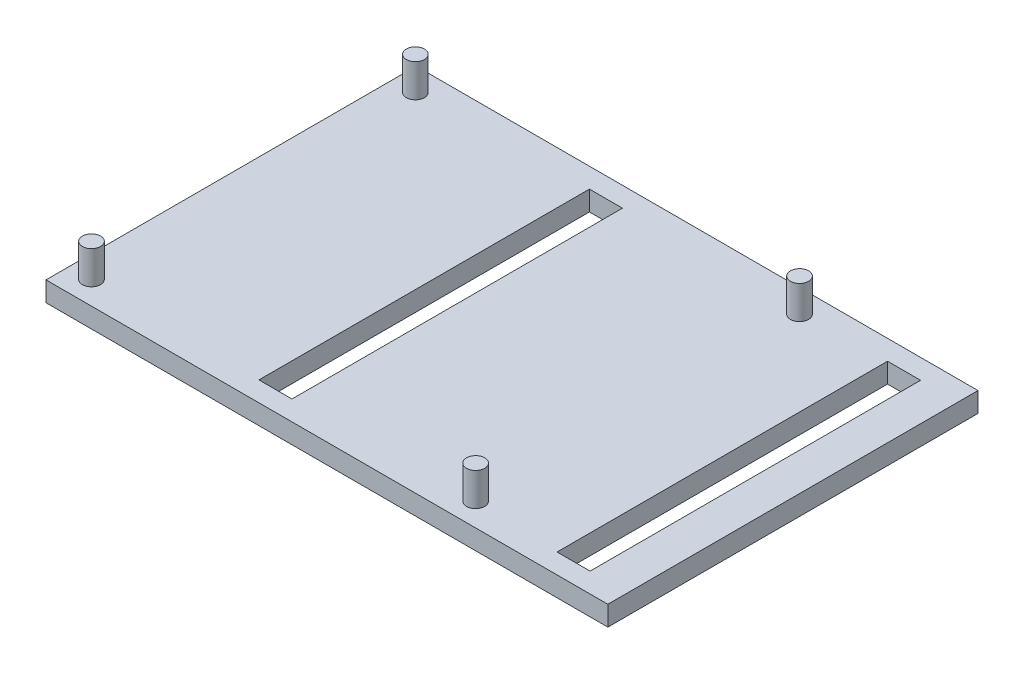
SolidWorks part; units mm, degrees
ref_plane "Plan de face" through (0, 0, 0) normal (0, 0, 1) x (1, 0, 0)
ref_plane "Plan de dessus" through (0, 0, 0) normal (0, 1, 0) x (1, 0, 0)
ref_plane "Plan de droite" through (0, 0, 0) normal (1, 0, 0) x (0, 0, -1)
sketch "Esquisse1" plane through (0, 0, 0) normal (0, 1, 0) x (1, 0, 0)
  line L0 (-42.5, 0) -> (16.7085, 0) construction
  line L1 (42.5, 28) -> (-42.5, 28)
  line L2 (42.5, 28) -> (42.5, -28)
  line L3 (42.5, -28) -> (-42.5, -28)
  line L4 (-42.5, 28) -> (-42.5, -28)
  line L5 (42.5, 28) -> (-42.5, -28) construction
  line L6 (42.5, -28) -> (-42.5, 28) construction
  line L7 (11.7629, 23.5878) -> (11.7629, -18.0665) construction
  line L8 (-8.2876, 25) -> (-13.2876, 25)
  line L9 (-8.2876, 25) -> (-8.2876, -25)
  line L10 (-8.2876, -25) -> (-13.2876, -25)
  line L11 (-13.2876, 25) -> (-13.2876, -25)
  line L12 (-8.2876, 25) -> (-13.2876, -25) construction
  line L13 (-8.2876, -25) -> (-13.2876, 25) construction
  line L14 (31.8133, -25) -> (36.8133, -25)
  line L15 (31.8133, 25) -> (31.8133, -25)
  line L16 (31.8133, 25) -> (36.8133, 25)
  line L17 (36.8133, 25) -> (36.8133, -25)
  point P0 (0, 0)
  point P6 (-10.7876, 0)
  dimension "D1" = 85
  dimension "D2" = 56
  dimension "D3" = 5
  dimension "D4" = 50
extrude "BASE" add sketch "Esquisse1" along normal blind 3
sketch "Esquisse2" plane through (0, 3, 0) normal (0, 1, 0) x (1, 0, 0)
  line L0 (-39, 28.0707) -> (-39, -34.4186) construction
  line L1 (-42.5, 0) -> (-27.7014, 0) construction
  line L2 (-42.5, 28) -> (-42.5, -28) construction
  line L3 (19, 24.5) -> (19, -25.5337) construction
  circle A0 centre (-39.1183, 24.5) radius 1.375
  circle A1 centre (-39.1183, -24.5) radius 1.375
  circle A2 centre (19, 24.5) radius 1.375
  circle A3 centre (19, -24.5) radius 1.375
  point P0 (-39.1183, 24.5)
  point P1 (-39, -24.5)
  point P2 (19, -24.5)
  point P3 (19, 24.5)
  dimension "D4" = 2.75
  dimension "D8" = 2.75
  dimension "D1" = 24.5
  dimension "D2" = 24.5
  dimension "D3" = 3.5
  dimension "D5" = 24.5
  dimension "D6" = 24.5
  dimension "D7" = 58
extrude "BOSS - ENTRETOISE" add sketch "Esquisse2" along normal blind 5
sketch "Esquisse3" plane through (0, 0, 0) normal (0, -1, 0) x (1, 0, 0)
  circle A0 centre (19, 24.5) radius 1.375 construction
  circle A1 centre (19, 24.5) radius 1.375
  circle A2 centre (19, -24.5) radius 1.375 construction
  circle A3 centre (-39.1183, -24.5) radius 1.375 construction
  circle A4 centre (-39.1183, 24.5) radius 1.375 construction
  circle A5 centre (19, -24.5) radius 1.375
  circle A6 centre (-39.1183, -24.5) radius 1.375
  circle A7 centre (-39.1183, 24.5) radius 1.375
extrude "Enlèv. mat.-Extru.1" cut sketch "Esquisse3" against normal up to surface (3 mm away) up to face at (19, 3, -25.875)
ref_axis "AXE ENTRETOISE 1" through (19, 3, -24.5) along (0, -1, 0)
ref_axis "AXE ENTRETOISE 2" through (-39.1183, 3, -24.5) along (0, -1, 0)
ref_plane "PLAN ENTRETOISE" through (0, 0, -24.5) normal (0, 0, 1) x (1, 0, 0)
sketch "Esquisse4" plane through (0, 0, -24.5) normal (0, 0, 1) x (1, 0, 0)
  line L0 (19, 3) -> (19, 0) construction
  line L1 (42.5, 0) -> (-42.5, 0) construction
  line L2 (20.375, 3) -> (20.375, 0) construction
  line L3 (19, 2) -> (20.375, 2)
  line L4 (21.76, 0) -> (19, 0)
  line L6 (42.5, 3) -> (-42.5, 3) construction
  line L7 (19, 3) -> (19, 0) construction
  line L9 (20.375, 2) -> (21.76, 0)
  line L14 (19, 2) -> (19, 0)
  point P0 (19, 2)
  dimension "D1" = 2
  dimension "D2" = 1.375
  dimension "D3" = 2.76
revolve "VIDE VIS 1" cut sketch "Esquisse4" angle 360 about L7
sketch "Esquisse5" plane through (0, 0, -24.5) normal (0, 0, 1) x (1, 0, 0)
  line L0 (42.5, 0) -> (-42.5, 0) construction
  line L1 (-39.1183, 2) -> (-37.7433, 2)
  line L2 (-37.7433, 2) -> (-36.3583, 0)
  line L3 (-39.1183, 3) -> (-39.1183, 0) construction
  line L4 (-36.3583, 0) -> (-39.1183, 0)
  line L5 (-39.1183, 0) -> (-39.1183, 2)
  line L6 (-37.7433, 3) -> (-37.7433, -0.329) construction
  point P0 (-39.1183, 2)
  point P5 (-36.3583, 0)
  point P7 (-39.1183, 0)
  dimension "D1" = 2
  dimension "D2" = 2.76
revolve "VIDE VIS 2" cut sketch "Esquisse5" angle 360 about axis through (-39.1183, 3, -24.5) along (0, -1, 0)
mirror "SYM VIS" about plane through (0, 0, 0) normal (0, 0, 1) of "VIDE VIS 2", "VIDE VIS 1"
